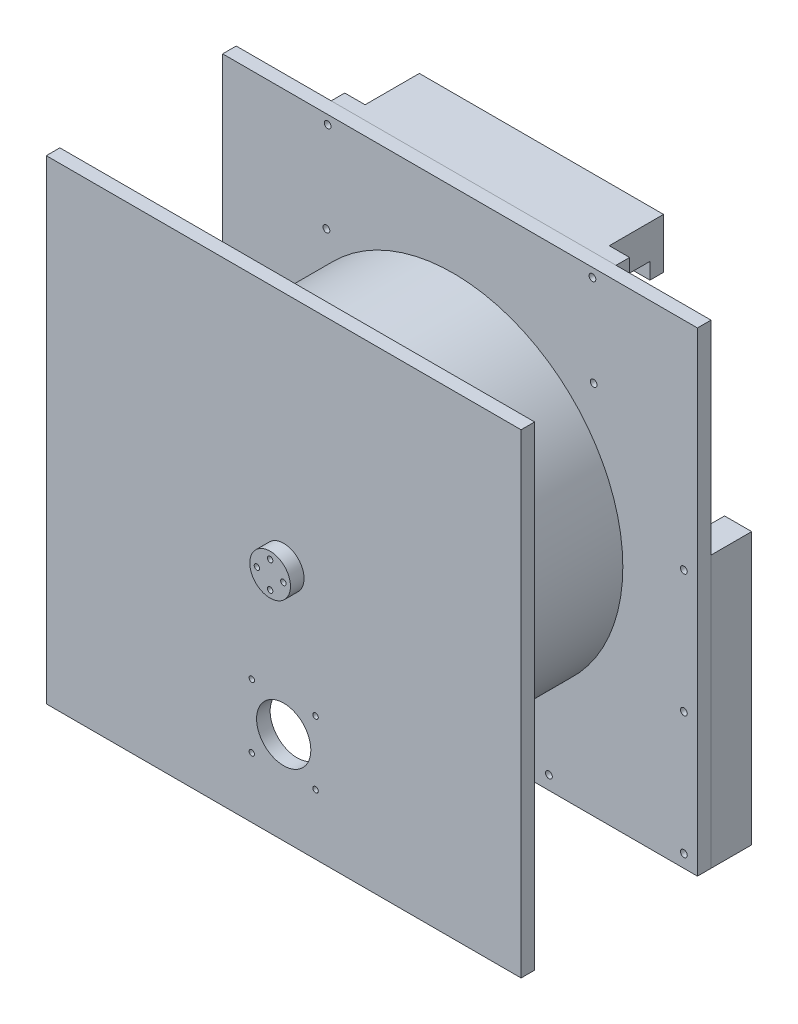
SolidWorks part; units mm, degrees
ref_plane "Front Plane" through (0, 0, 0) normal (0, 0, 1) x (1, 0, 0)
ref_plane "Top Plane" through (0, 0, 0) normal (0, 1, 0) x (1, 0, 0)
ref_plane "Right Plane" through (0, 0, 0) normal (1, 0, 0) x (0, 0, -1)
sketch "Sketch1" plane through (0, 0, 0) normal (0, 0, 1) x (1, 0, 0)
  line L5 (-175, 175) -> (175, 175)
  line L6 (-175, 175) -> (-175, -175)
  line L7 (-175, -175) -> (175, -175)
  line L8 (175, 175) -> (175, -175)
  line L9 (-175, 175) -> (175, -175) construction
  line L10 (-175, -175) -> (175, 175) construction
  point P0 (0, 0)
  dimension "D1" = 350
extrude "Boss-Extrude1" add sketch "Sketch1" along normal blind 10 from offset 60
extrude "Boss-Extrude2" add sketch "Sketch1<2>" against normal blind 10 from offset 60 separate body offset against normal yes
sketch "Sketch1<2>" plane through (0, 0, 0) normal (0, 0, 1) x (1, 0, 0) same geometry as "Sketch1"
ref_axis "Axis1" through (0, 0, -77) along (0, 0, 1)
sketch "Sketch2" plane through (0, 0, 0) normal (0, 1, 0) x (1, 0, 0)
  line L0 (-125, 55) -> (-125, -35)
  line L1 (-125, -35) -> (-82, -35)
  line L2 (-82, -35) -> (-82, -55)
  line L3 (-82, -55) -> (-10, -55)
  line L5 (-125, 55) -> (-10, 55)
  line L6 (-10, 55) -> (-10, -55)
  line L8 (0, -59.5538) -> (0, 59.9437) construction
  line L9 (0, 77) -> (0, -77) construction
  line L10 (175, 60) -> (-175, 60) construction
  line L11 (175, -60) -> (-175, -60) construction
  point P15 (-40, -28.2737)
  dimension "D1" = 20
  dimension "D2" = 5
  dimension "D3" = 5
  dimension "D4" = 164
  dimension "D5" = 250
  dimension "D6" = 20
revolve "Revolve1" add sketch "Sketch2" angle 360 about L8
sketch "Sketch3" plane through (0, 0, 0) normal (1, 0, 0) x (0, 0, -1)
  line L0 (70, 95) -> (70, 175)
  line L1 (70, -175) -> (70, 175) construction
  line L2 (70, 175) -> (120, 175)
  line L3 (120, 175) -> (120, 175.0843)
  line L4 (110, 150) -> (80, 150)
  line L5 (80, 150) -> (80, 95)
  line L6 (80, 95) -> (70, 95)
  line L7 (120, 175.0843) -> (120, 138)
  line L8 (120, 138) -> (110, 138)
  line L9 (110, 138) -> (110, 150)
  line L10 (80, 150) -> (80, 175)
  dimension "D1" = 80
  dimension "D2" = 25
  dimension "D3" = 10
  dimension "D4" = 10
  dimension "D5" = 12
  dimension "D6" = 30
extrude "Boss-Extrude3" add sketch "Sketch3" along normal mid plane 180 separate body contours L9 L8 L7 L2 L0 L6 L5 L4 | L5 L10 L2 L0 L6 region at (0, 135, -75) region at (0, 160.5179, -101.6071)
extrude "Boss-Extrude4" add sketch "Sketch3<3>" along normal mid plane 210 contours L5 L10 L2 L0 L6 region at (0, 135, -75)
sketch "Sketch3<3>" plane through (0, 0, 0) normal (1, 0, 0) x (0, 0, -1) same geometry as "Sketch3"
sketch "Sketch4" plane through (0, 0, -70) normal (0, 0, -1) x (-1, 0, 0)
  line L0 (-175, -175) -> (-175, 175) construction
  line L1 (-175, 25) -> (-155, 25)
  line L2 (-175, 25) -> (-175, -175)
  line L3 (-175, -175) -> (-155, -175)
  line L4 (-155, 25) -> (-155, -175)
  line L5 (175, -175) -> (-175, -175) construction
  line L6 (-175, 15.5) -> (-155, 15.5) construction
  line L7 (-165, 15.5) -> (-165, -165.5) construction
  circle A0 centre (-165, 15.5) radius 2.5
  circle A1 centre (-165, -165.5) radius 2.5
  circle A2 centre (-165, -75) radius 2.5
  point P14 (-165, -75)
  point P15 (-165, 15.5)
  point P16 (-175, -75)
  dimension "D3" = 5
  dimension "D4" = 7
  dimension "D1" = 200
  dimension "D2" = 20
extrude "Cut-Extrude1" cut sketch "Sketch4" against normal up to next (10 mm away) contours A0 | A2 | A1
extrude "Boss-Extrude5" add sketch "Sketch4<4>" along normal blind 30 separate body
sketch "Sketch4<4>" plane through (0, 0, -70) normal (0, 0, -1) x (-1, 0, 0) same geometry as "Sketch4"
sketch "Sketch5" plane through (0, 0, -70) normal (0, 0, 1) x (1, 0, 0)
  circle A0 centre (165, 15.5) radius 4
  circle A1 centre (165, -75) radius 4
  circle A2 centre (165, -165.5) radius 4
  dimension "D1" = 8
extrude "Cut-Extrude2" cut sketch "Sketch5" against normal blind 7
mirror "Mirror4" about plane through (0, 0, 0) normal (1, 0, 0) of bodies 108
sketch "Sketch6" plane through (0, 0, -70) normal (0, 0, -1) x (-1, 0, 0)
  line L0 (0, 4.5) -> (0, 15) construction
  circle A0 centre (0, 0) radius 4.5
  circle A1 centre (0, 0) radius 15
  circle A2 centre (0, 9.75) radius 2
  circle A3 centre (9.75, 0) radius 2
  circle A4 centre (0, -9.75) radius 2
  circle A5 centre (-9.75, 0) radius 2
  point P8 (-12.0044, -2.1368)
  point P9 (0, 0)
  point P10 (0, 0)
  point P17 (0, 0)
  dimension "D1" = 9
  dimension "D2" = 30
  dimension "D3" = 4
  dimension "D4" = 4
extrude "Cut-Extrude3" cut sketch "Sketch6" against normal through all contours A0
extrude "Cut-Extrude4" cut sketch "Sketch6<3>" against normal up to next (10 mm away) contours A2 | A3 | A4 | A5
sketch "Sketch6<3>" plane through (0, 0, -70) normal (0, 0, -1) x (-1, 0, 0) same geometry as "Sketch6"
extrude "Boss-Extrude6" add sketch "Sketch6<4>" along normal blind 5 separate body
sketch "Sketch6<4>" plane through (0, 0, -70) normal (0, 0, -1) x (-1, 0, 0) same geometry as "Sketch6"
extrude "Boss-Extrude7" add sketch "Sketch6<5>" along normal blind 5 from offset 5 contours A1 | A5 | A2 | A3 | A4
sketch "Sketch6<5>" plane through (0, 0, -70) normal (0, 0, -1) x (-1, 0, 0) same geometry as "Sketch6"
mirror "Mirror2" about plane through (0, 0, 0) normal (0, 0, 1) of "Cut-Extrude4"
mirror "Mirror3" about plane through (0, 0, 0) normal (0, 0, 1) of bodies 118
sketch "Sketch7" plane through (0, 0, -70) normal (0, 0, -1) x (-1, 0, 0)
  line L0 (175, -175) -> (-175, -175) construction
  line L1 (-75, -155) -> (75, -155)
  line L2 (-75, -155) -> (-75, -175)
  line L3 (-75, -175) -> (75, -175)
  line L4 (75, -155) -> (75, -175)
  line L5 (-155, 25) -> (-175, 25) construction
  line L6 (-65.5, -165) -> (65.5, -165) construction
  line L7 (-65.5, -155) -> (-65.5, -175) construction
  circle A0 centre (-65.5, -165) radius 2.5
  circle A1 centre (65.5, -165) radius 2.5
  circle A2 centre (0, -165) radius 2.5
  circle A3 centre (-165, -75) radius 2.5 construction
  point P4 (0, -155)
  point P14 (-65.5, -165)
  point P19 (0, 0)
  point P20 (0, -175)
  dimension "D2" = 7
  dimension "D1" = 150
extrude "Cut-Extrude5" cut sketch "Sketch7" against normal up to next (10 mm away) contours A0 | A2 | A1
extrude "Boss-Extrude8" add sketch "Sketch7<3>" along normal blind 10 separate body
sketch "Sketch7<3>" plane through (0, 0, -70) normal (0, 0, -1) x (-1, 0, 0) same geometry as "Sketch7"
sketch "Sketch8" plane through (0, 0, 0) normal (0, 0, 1) x (1, 0, 0)
  line L1 (-23.5, -130.5) -> (23.5, -130.5) construction
  line L2 (-23.5, -130.5) -> (-23.5, -83.5) construction
  line L3 (-23.5, -83.5) -> (23.5, -83.5) construction
  line L4 (23.5, -130.5) -> (23.5, -83.5) construction
  line L5 (-23.5, -130.5) -> (23.5, -83.5) construction
  line L6 (-23.5, -83.5) -> (23.5, -130.5) construction
  circle A0 centre (0, -107) radius 25 construction
  circle A1 centre (0, 0) radius 82 construction
  circle A2 centre (0, 0) radius 82 construction
  circle A3 centre (-23.5, -83.5) radius 2
  circle A4 centre (23.5, -83.5) radius 2
  circle A5 centre (-23.5, -130.5) radius 2
  circle A6 centre (23.5, -130.5) radius 2
  circle A7 centre (0, -107) radius 20
  dimension "D1" = 50
  dimension "D2" = 4
  dimension "D4" = 40
  dimension "D3" = 47
extrude "Cut-Extrude6" cut sketch "Sketch8" against normal up to next (55 mm away) from surface contours A7 | A4 | A6 | A5 | A3 starting at face at (-11.75, 0, 70)
sketch "Sketch9" plane through (0, 0, -80) normal (0, 0, -1) x (-1, 0, 0)
  line L0 (-97.5884, 168.5) -> (-98.5, 101.5) construction
  line L1 (-105, 175) -> (-90, 175) construction
  line L2 (0, 138) -> (0, 95) construction
  line L3 (-90, 138) -> (90, 138) construction
  line L4 (-105, 95) -> (105, 95) construction
  line L5 (-98.5, 101.5) -> (0, 101.5) construction
  line L7 (-105, 175) -> (-105, 95) construction
  circle A0 centre (-97.5884, 168.5) radius 2.5
  circle A1 centre (-98.5, 101.5) radius 2.5
  circle A2 centre (-165, 15.5) radius 2.5 construction
  circle A3 centre (0, 101.5) radius 2.5
  circle A4 centre (97.5884, 168.5) radius 2.5
  circle A5 centre (98.5, 101.5) radius 2.5
  point P6 (-97.5, 175)
  point P19 (0, 101.5)
  point P24 (0, 101.5)
  dimension "D1" = 4
  dimension "D2" = 4
  dimension "D3" = 4
extrude "Cut-Extrude7" cut sketch "Sketch9" against normal up to surface (20 mm away) up to face at (68, -165, -60)
